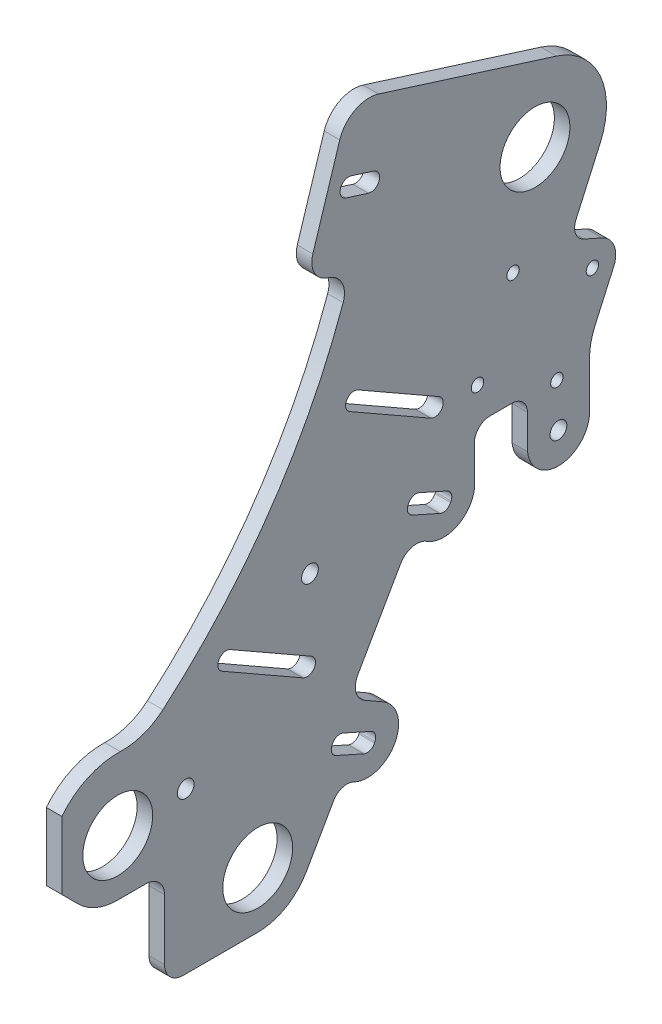
SolidWorks part; units mm, degrees
ref_plane "Front Plane" through (0, 0, 0) normal (0, 0, 1) x (1, 0, 0)
ref_plane "Top Plane" through (0, 0, 0) normal (0, 1, 0) x (1, 0, 0)
ref_plane "Right Plane" through (0, 0, 0) normal (1, 0, 0) x (0, 0, -1)
sketch "Sketch1" plane through (0, 0, 0) normal (1, 0, 0) x (0, 0, -1)
  line L0 (0, 0) -> (-57.2178, 40.0643) construction
  line L1 (55, 0) -> (-55, 0) construction
  line L2 (0, 0) -> (113.3671, 198.5091) construction
  line L3 (113.3671, 198.5091) -> (49.679, 218.5899) construction
  line L4 (99.338, 182.3162) -> (24.13, 14.224) construction
  line L5 (30.5555, 28.5852) -> (30.3602, 28.1486)
  line L6 (36.1341, 219.132) -> (45.2183, 216.2678)
  line L7 (38.2727, 225.9148) -> (47.3569, 223.0506)
  line L8 (34.9378, 30.2582) -> (46.2714, 25.1873)
  line L9 (47.9444, 20.8051) -> (47.749, 20.3685)
  line L10 (43.3668, 18.6955) -> (32.0332, 23.7664)
  line L11 (104.397, 158.4994) -> (136.8574, 143.9792) construction
  line L12 (136.8574, 143.9792) -> (122.3372, 111.5188) construction
  line L14 (61.6761, 98.1406) -> (61.4807, 97.704)
  line L15 (66.0583, 99.8136) -> (77.3919, 94.7427)
  line L16 (79.0649, 90.3605) -> (78.8696, 89.9239)
  line L17 (74.4873, 88.2509) -> (63.1537, 93.3218)
  line L18 (72.429, 126.8253) -> (39.3441, 145.7198) construction
  line L19 (20.2106, 60.9985) -> (-12.8742, 79.893) construction
  line L20 (70.7285, 123.8476) -> (37.6436, 142.7421)
  line L21 (74.1295, 129.8029) -> (41.0446, 148.6974)
  line L22 (18.5101, 58.0208) -> (-14.5747, 76.9153)
  line L23 (122.3372, 111.5188) -> (89.8768, 126.039) construction
  line L24 (89.8768, 126.039) -> (104.397, 158.4994) construction
  line L25 (104.397, 158.4994) -> (122.3372, 111.5188) construction
  line L26 (21.9112, 63.9761) -> (-11.1737, 82.8706)
  circle A0 centre (0, 0) radius 14.2875
  circle A1 centre (-57.2178, 40.0643) radius 14.2875
  circle A2 centre (113.3671, 198.5091) radius 14.2875
  arc A3 (45.2183, 216.2678) -> (47.3569, 223.0506) centre (46.2876, 219.6592) ccw
  arc A4 (38.2727, 225.9148) -> (36.1341, 219.132) centre (37.2034, 222.5234) ccw
  arc A17 (46.2714, 25.1873) -> (47.9444, 20.8051) centre (44.9167, 22.1597) cw
  arc A18 (47.749, 20.3685) -> (43.3668, 18.6955) centre (44.7214, 21.7231) cw
  arc A19 (32.0332, 23.7664) -> (30.3602, 28.1486) centre (33.3878, 26.794) cw
  arc A20 (30.5555, 28.5852) -> (34.9378, 30.2582) centre (33.5831, 27.2306) cw
  arc A21 (74.4873, 88.2509) -> (78.8696, 89.9239) centre (75.842, 91.2785) ccw
  arc A22 (79.0649, 90.3605) -> (77.3919, 94.7427) centre (76.0373, 91.7151) ccw
  arc A23 (63.1537, 93.3218) -> (61.4807, 97.704) centre (64.5084, 96.3494) cw
  arc A24 (61.6761, 98.1406) -> (66.0583, 99.8136) centre (64.7037, 96.786) cw
  circle A25 centre (-29.4365, 42.7262) radius 3.429
  circle A26 centre (21.3635, 93.5262) radius 3.429
  circle A27 centre (122.9635, 93.5262) radius 3.429
  arc A28 (70.7285, 123.8476) -> (74.1295, 129.8029) centre (72.429, 126.8253) ccw
  arc A29 (41.0446, 148.6974) -> (37.6436, 142.7421) centre (39.3441, 145.7198) ccw
  circle A32 centre (104.397, 158.4994) radius 2.54
  circle A33 centre (136.8574, 143.9792) radius 2.54
  circle A34 centre (122.3372, 111.5188) radius 2.54
  circle A35 centre (89.8768, 126.039) radius 2.54
  arc A36 (18.5101, 58.0208) -> (21.9112, 63.9761) centre (20.2106, 60.9985) ccw
  arc A37 (-11.1737, 82.8706) -> (-14.5747, 76.9153) centre (-12.8742, 79.893) ccw
  point P30 (113.3671, 135.0091)
  point P36 (3.6682, 70.4457)
  point P47 (49.299, 23.8327)
  point P54 (29.0056, 25.121)
  point P57 (31.9101, 31.6128)
  point P62 (80.4195, 93.3881)
  point P65 (60.1261, 94.6764)
  point P68 (63.0307, 101.1682)
  point P78 (55.8866, 136.2725)
  dimension "D2" = 28.575
  dimension "D4" = 228.6
  dimension "D10" = 13.081
  dimension "D7" = 3.556
  dimension "D8" = 9.525
  dimension "D11" = 65.895
  dimension "D18" = 35.56
  dimension "D20" = 38.1
  dimension "D21" = 24.1
  dimension "D27" = 7.112
  dimension "D22" = 5.08
  dimension "D29" = 3.3168
  dimension "D30" = 6.858
  dimension "D33" = 6.858
  dimension "D36" = 6.858
  dimension "D40" = 3.429
  dimension "D25" = 3.429
  dimension "D26" = 50.8
  dimension "D1" = 35
  dimension "D3" = 69.85
  dimension "D5" = 60.27
  dimension "D6" = 17.5
  dimension "D9" = 66.7788
  dimension "D12" = 14.224
  dimension "D13" = 184.15
  dimension "D14" = 24.13
  dimension "D15" = 7.112
  dimension "D16" = 165.1
  dimension "D17" = 19.05
  dimension "D19" = 63.5
  dimension "D23" = 19.05
  dimension "D24" = 76.2
  dimension "D28" = 88.9
  dimension "D31" = 27.7812
  dimension "D32" = 2.6619
  dimension "D34" = 78.5812
  dimension "D35" = 53.4619
  dimension "D37" = 180.1812
  dimension "D38" = 53.4619
  dimension "D39" = 82.55
  dimension "D41" = 38.1
sketch "Sketch2" plane through (0, 0, 0) normal (1, 0, 0) x (0, 0, -1)
  line L1 (-80.0778, 30.5954) -> (-80.0778, 58.2479)
  line L2 (19.8509, -11.3367) -> (31.0118, 8.2063)
  line L3 (0, 0) -> (113.3671, 198.5091) construction
  line L9 (113.3671, 198.5091) -> (49.679, 218.5899) construction
  line L11 (49.4775, 249.281) -> (122.1507, 226.3672)
  line L12 (33.5463, 240.9877) -> (22.5477, 206.1046)
  line L13 (28.5188, 194.6341) -> (29.0827, 194.4563)
  line L14 (110.3329, 92.1997) -> (110.288, 92.1997)
  line L15 (88.5941, 92.1997) -> (88.5941, 106.1697)
  line L16 (110.288, 92.1997) -> (110.288, 106.1697)
  line L17 (103.938, 112.5197) -> (94.9441, 112.5197)
  line L18 (88.5941, 92.1997) -> (88.5941, 89.8131)
  line L19 (58.4048, 78.4274) -> (40.9124, 47.8643)
  line L20 (43.7407, 37.4658) -> (51.2253, 33.1821)
  line L23 (-38.1, 9.5843) -> (-38.1, -15.24)
  line L24 (-30.48, -22.86) -> (0, -22.86)
  line L25 (-57.2178, 17.2043) -> (-45.72, 17.2043)
  line L26 (-73.3822, 23.8999) -> (-80.0778, 30.5954)
  line L27 (104.397, 158.4994) -> (136.8574, 143.9792) construction
  line L28 (136.8574, 143.9792) -> (122.3372, 111.5188) construction
  line L29 (122.3372, 111.5188) -> (89.8768, 126.039) construction
  line L30 (89.8768, 126.039) -> (104.397, 158.4994) construction
  line L31 (104.397, 158.4994) -> (122.3372, 111.5188) construction
  line L32 (140.031, 186.5818) -> (130.1045, 164.3908)
  line L33 (140.7468, 152.6739) -> (133.3081, 156.0014)
  line L34 (145.5521, 140.0898) -> (137.8775, 122.9329)
  line L35 (135.6635, 93.5262) -> (135.6635, 112.5613)
  arc A1 (0, -22.86) -> (19.8509, -11.3367) centre (0, 0) ccw
  arc A2 (39.3228, 10.758) -> (51.2253, 33.1821) centre (44.9167, 22.1597) ccw
  arc A3 (69.1503, 81.0446) -> (88.5941, 89.8131) centre (76.0373, 91.7151) ccw
  arc A7 (31.0118, 8.2063) -> (39.3228, 10.758) centre (36.5259, 5.0572) cw
  arc A13 (140.031, 186.5818) -> (122.1507, 226.3672) centre (113.3671, 198.5091) ccw
  arc A15 (33.5463, 240.9877) -> (49.4775, 249.281) centre (45.6585, 237.1687) cw
  arc A16 (34.9451, 182.6622) -> (-38.7381, 75.3772) centre (-204.3307, 268.0513) cw
  arc A17 (-56.1886, 69.2562) -> (-80.0778, 58.2479) centre (-57.2178, 40.0643) ccw
  arc A18 (29.0827, 194.4563) -> (34.9451, 182.6622) centre (26.3331, 185.7355) cw
  arc A19 (22.5477, 206.1046) -> (28.5188, 194.6341) centre (31.2685, 203.3549) ccw
  arc A21 (-38.7381, 75.3772) -> (-56.1886, 69.2562) centre (-55.2938, 94.6404) cw
  arc A22 (110.3329, 92.1997) -> (135.6635, 93.5262) centre (122.9635, 93.5262) ccw
  arc A25 (110.288, 106.1697) -> (103.938, 112.5197) centre (103.938, 106.1697) ccw
  arc A26 (88.5941, 106.1697) -> (94.9441, 112.5197) centre (94.9441, 106.1697) cw
  arc A27 (58.4048, 78.4274) -> (69.1503, 81.0446) centre (65.0182, 74.6423) cw
  arc A28 (43.7407, 37.4658) -> (40.9124, 47.8643) centre (47.5258, 44.0792) cw
  arc A29 (-73.3822, 23.8999) -> (-57.2178, 17.2043) centre (-57.2178, 40.0643) ccw
  arc A30 (-30.48, -22.86) -> (-38.1, -15.24) centre (-30.48, -15.24) cw
  arc A31 (-38.1, 9.5843) -> (-45.72, 17.2043) centre (-45.72, 9.5843) ccw
  arc A32 (145.5521, 140.0898) -> (140.7468, 152.6739) centre (136.8574, 143.9792) ccw
  arc A34 (135.6635, 112.5613) -> (137.8775, 122.9329) centre (161.0635, 112.5613) cw
  arc A35 (133.3081, 156.0014) -> (130.1045, 164.3908) centre (135.901, 161.7979) cw
  point P24 (84.2401, 101.4107)
  point P25 (-38.1, -22.86)
  point P27 (71.8548, 79.7236)
  point P30 (46.1964, 34.7951)
  point P41 (110.288, 112.5197)
  point P62 (37.3653, 253.0999)
  point P66 (37.9664, 191.6553)
  point P69 (19.798, 197.3838)
  point P71 (88.5941, 112.5197)
  point P74 (-48.0067, 67.784)
  point P86 (113.3671, 135.0091)
  point P92 (37.1273, 41.2509)
  dimension "D2" = 45.72
  dimension "D4" = 25.4
  dimension "D5" = 21.6939
  dimension "D6" = 38.1
  dimension "D7" = 19.05
  dimension "D8" = 25.4
  dimension "D9" = 6.35
  dimension "D10" = 6.35
  dimension "D11" = 58.42
  dimension "D15" = 12.7
  dimension "D17" = 9.144
  dimension "D18" = 254.0555
  dimension "D19" = 2.3866
  dimension "D20" = 25.4
  dimension "D21" = 25.4
  dimension "D28" = 6.35
  dimension "D30" = 7.62
  dimension "D31" = 7.62
  dimension "D33" = 22.86
  dimension "D34" = 29.21
  dimension "D35" = 7.62
  dimension "D3" = 22.86
  dimension "D12" = 88.9
  dimension "D14" = 58.42
  dimension "D16" = 19.05
  dimension "D22" = 180.1812
  dimension "D23" = 53.4619
  dimension "D25" = 20.32
  dimension "D26" = 20.32
  dimension "D27" = 12.6305
  dimension "D29" = 16.2437
  dimension "D32" = 35.2148
  dimension "D36" = 9.4689
  dimension "D37" = 35.56
  dimension "D38" = 63.5
  dimension "D39" = 24.1
extrude "Boss-Extrude1" add sketch "Sketch2" along normal blind 3.175 and the other way blind 3.175
extrude "Cut-Extrude1" cut sketch "Sketch1" against normal through all and the other way through all
